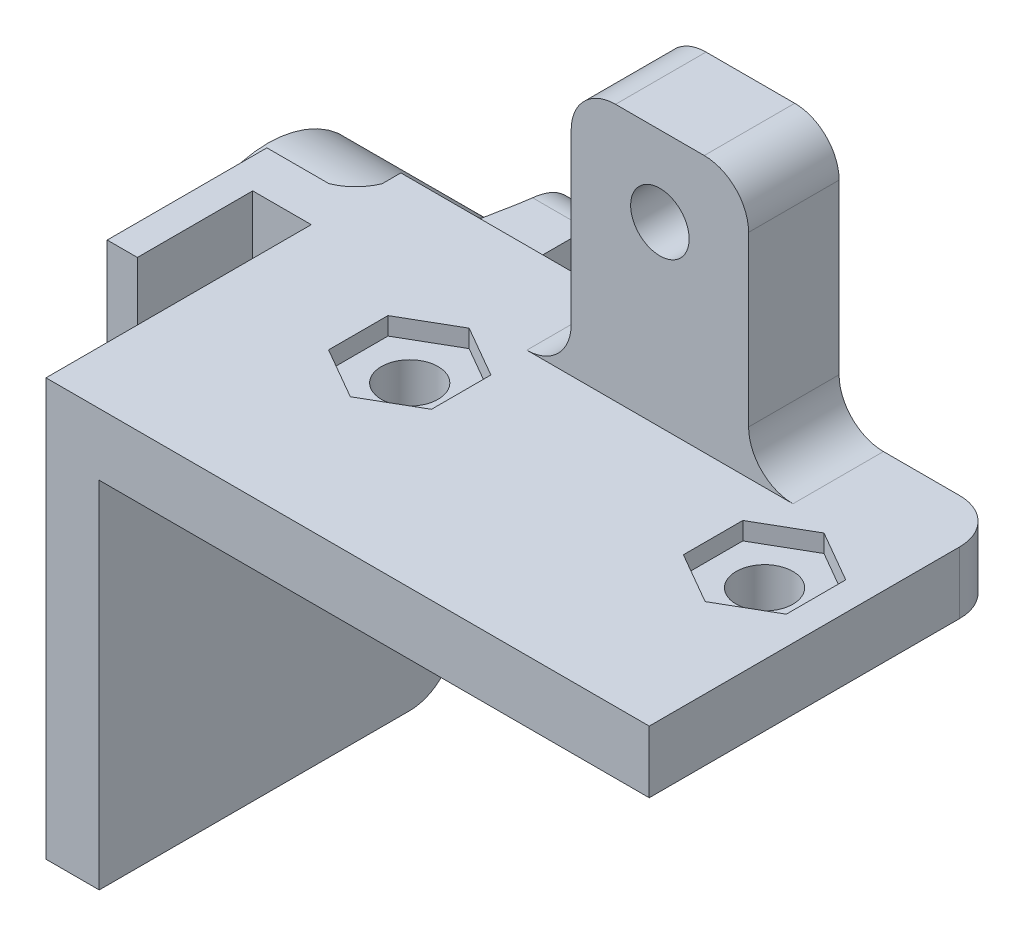
SolidWorks part; units mm, degrees
ref_plane "Alzado" through (0, 0, 0) normal (0, 0, 1) x (1, 0, 0)
ref_plane "Planta" through (0, 0, 0) normal (0, 1, 0) x (1, 0, 0)
ref_plane "Vista lateral" through (0, 0, 0) normal (1, 0, 0) x (0, 0, -1)
sketch "Croquis1" plane through (0, 0, 0) normal (0, 1, 0) x (1, 0, 0)
  line L1 (0, 0) -> (34, 0)
  line L2 (0, 0) -> (0, -20)
  line L3 (0, -20) -> (34, -20)
  line L4 (34, 0) -> (34, -20)
  dimension "D1" = 34
  dimension "D2" = 20
extrude "Saliente-Extruir1" add sketch "Croquis1" along normal blind 3.5
sketch "Croquis2" plane through (0, 3.5, 0) normal (0, 1, 0) x (1, 0, 0)
  line L0 (0, 0) -> (0, -20) construction
  line L1 (0, -20) -> (34, -20) construction
  circle A0 centre (9.5, -9) radius 1.6
  circle A1 centre (29.5, -9) radius 1.6
  dimension "D1" = 3.2
  dimension "D2" = 3.2
  dimension "D3" = 20
  dimension "D4" = 9.5
  dimension "D5" = 11
extrude "Cortar-Extruir1" cut sketch "Croquis2" against normal up to surface (3.5 mm away) up to face at (17, 0, 10)
sketch "Croquis3" plane through (0, 0, 0) normal (0, -1, 0) x (1, 0, 0)
  line L0 (0, 20) -> (34, 20) construction
  line L1 (0, 0) -> (3, 0)
  line L2 (0, 0) -> (0, 20)
  line L3 (0, 20) -> (3, 20)
  line L4 (3, 0) -> (3, 20)
  dimension "D1" = 3
extrude "Saliente-Extruir2" add sketch "Croquis3" along normal blind 20
sketch "Croquis4" plane through (0, 0, 0) normal (0, 0, -1) x (-1, 0, 0)
  line L0 (-3, -20) -> (-3, 0) construction
  line L1 (-3, -1.5) -> (0, -1.5)
  line L2 (-3, -1.5) -> (-3, -15.5)
  line L3 (-3, -15.5) -> (0, -15.5)
  line L4 (0, -1.5) -> (0, -15.5)
  line L5 (0, 3.5) -> (0, -20) construction
  line L6 (-34, 3.5) -> (0, 3.5) construction
  dimension "D1" = 14
  dimension "D2" = 5
extrude "Saliente-Extruir3" add sketch "Croquis4" along normal blind 10
sketch "Croquis5" plane through (0, 0, 0) normal (-1, 0, 0) x (0, 0, 1)
  line L0 (-10, -15.5) -> (0, -15.5) construction
  line L1 (0, 3.5) -> (0, -1.5) construction
  circle A0 centre (-3.5, -8.3) radius 6
  dimension "D1" = 12
  dimension "D2" = 7.2
  dimension "D3" = 3.5
extrude "Saliente-Extruir4" add sketch "Croquis5" along normal blind 11
sketch "Croquis6" plane through (-11, 0, 0) normal (-1, 0, 0) x (0, 0, 1)
  circle A0 centre (-3.5, -8.3) radius 1
  dimension "D1" = 2
extrude "Cortar-Extruir2" cut sketch "Croquis6" against normal up to surface (14 mm away) up to face at (3, -9.25, 2.5)
sketch "Croquis7" plane through (3, 0, 0) normal (1, 0, 0) x (0, 0, -1)
  line L0 (10, -1.5) -> (10, -15.5) construction
  line L1 (7.1, -12.9) -> (0.8, -12.9)
  line L2 (7.1, -12.9) -> (7.1, -4.6)
  line L3 (7.1, -4.6) -> (0.8, -4.6)
  line L4 (0.8, -12.9) -> (0.8, -4.6)
  line L5 (10, -15.5) -> (0, -15.5) construction
  dimension "D1" = 8.3
  dimension "D2" = 6.3
  dimension "D3" = 2.9
  dimension "D4" = 2.6
extrude "Cortar-Extruir3" cut sketch "Croquis7" against normal blind 6.4
sketch "Croquis8" plane through (-11, 0, 0) normal (-1, 0, 0) x (0, 0, 1)
  circle A0 centre (-3.5, -8.3) radius 4.2
  dimension "D1" = 8.4
extrude "Cortar-Extruir4" cut sketch "Croquis8" against normal blind 6.3
fillet "Redondeo1" radius 1 1 edges at (-3.4, -8.3, -4.5)
sketch "Croquis9" plane through (0, 0, 0) normal (-1, 0, 0) x (0, 0, 1)
  line L0 (20, -20) -> (0, -20) construction
  line L1 (2.55, -20) -> (11.55, -20)
  line L2 (2.55, -20) -> (2.55, 3.5)
  line L3 (2.55, 3.5) -> (11.55, 3.5)
  line L4 (11.55, -20) -> (11.55, 3.5)
  line L5 (0, 3.5) -> (20, 3.5) construction
  line L6 (0, 3.5) -> (0, -1.5) construction
  dimension "D1" = 9
  dimension "D2" = 2.55
extrude "Saliente-Extruir7" add sketch "Croquis9" along normal blind 5
sketch "Croquis10" plane through (0, 0, 11.55) normal (0, 0, 1) x (1, 0, 0)
  line L5 (-5, -20) -> (0, -20) construction
  line L6 (0, 3.5) -> (-3.3, 3.5)
  line L7 (0, 3.5) -> (0, -20)
  line L8 (0, -20) -> (-3.3, -20)
  line L9 (-3.3, 3.5) -> (-3.3, -20)
  dimension "D1" = 3.3
extrude "Cortar-Extruir5" cut sketch "Croquis10" against normal blind 6.5
sketch "Croquis11" plane through (0, 3.5, 0) normal (0, 1, 0) x (1, 0, 0)
  line L0 (34, 0) -> (0, 0) construction
  line L1 (24.7, 0) -> (14.7, 0)
  line L2 (24.7, 0) -> (24.7, -5.1)
  line L3 (24.7, -5.1) -> (14.7, -5.1)
  line L4 (14.7, 0) -> (14.7, -5.1)
  line L5 (34, -20) -> (34, 0) construction
  dimension "D1" = 10
  dimension "D2" = 5.1
  dimension "D3" = 9.3
extrude "Saliente-Extruir8" add sketch "Croquis11" along normal blind 14.5
sketch "Croquis12" plane through (0, 0, 0) normal (0, 0, -1) x (-1, 0, 0)
  line L0 (-24.7, 18) -> (-24.7, 3.5) construction
  line L1 (-34, 3.5) -> (-24.7, 3.5) construction
  circle A0 centre (-19.7, 13.5) radius 1.65
  dimension "D2" = 3.3
  dimension "D1" = 5
  dimension "D3" = 10
extrude "Cortar-Extruir6" cut sketch "Croquis12" against normal up to surface (5.1 mm away) up to face at (19.7, 10.75, 5.1)
sketch "Croquis13" plane through (0, 0, 0) normal (0, 0, -1) x (-1, 0, 0)
  circle A0 centre (-19.7, 13.5) radius 3
  dimension "D1" = 6
extrude "Cortar-Extruir7" cut sketch "Croquis13" against normal blind 2.6
sketch "Croquis15" plane through (0, 3.5, 0) normal (0, 1, 0) x (1, 0, 0)
  line L1 (9.5, -5.6514) -> (6.6, -7.3257)
  line L2 (6.6, -7.3257) -> (6.6, -10.6743)
  line L3 (6.6, -10.6743) -> (9.5, -12.3486)
  line L4 (9.5, -12.3486) -> (12.4, -10.6743)
  line L5 (12.4, -10.6743) -> (12.4, -7.3257)
  line L6 (12.4, -7.3257) -> (9.5, -5.6514)
  line L7 (29.5, -5.6514) -> (26.6, -7.3257)
  line L8 (26.6, -7.3257) -> (26.6, -10.6743)
  line L9 (26.6, -10.6743) -> (29.5, -12.3486)
  line L10 (29.5, -12.3486) -> (32.4, -10.6743)
  line L11 (32.4, -10.6743) -> (32.4, -7.3257)
  line L12 (32.4, -7.3257) -> (29.5, -5.6514)
  circle A0 centre (9.5, -9) radius 2.9 construction
  circle A1 centre (29.5, -9) radius 2.9 construction
  dimension "D1" = 5.8
  dimension "D2" = 5.8
extrude "Cortar-Extruir9" cut sketch "Croquis15" against normal blind 1
fillet "Redondeo3" radius 2.5 2 edges at (1.5, -15.5, -10) (1.5, -1.5, -10)
fillet "Redondeo5" radius 2.5 1 edges at (0, -8.3, -9.5)
sketch "Croquis16" plane through (0, -20, 0) normal (0, -1, 0) x (1, 0, 0)
  line L0 (-5, 2.55) -> (0, 2.55) construction
  line L2 (0, 2.55) -> (0, 0) construction
  line L3 (0, 1.05) -> (0, 2.55)
  line L4 (0, 2.55) -> (-1.5, 2.55)
  arc A0 (-1.5, 2.55) -> (0, 1.05) centre (-2.5583, -0.0083) cw
  dimension "D1" = 1.5
  dimension "D2" = 1.5
extrude "Saliente-Extruir9" add sketch "Croquis16" against normal up to surface (23.5 mm away) up to face at (9.5, 3.5, 9)
fillet "Redondeo6" radius 2.5 6 edges at (14.7, 3.5, 2.55) (24.7, 3.5, 2.55) (24.7, 18, 2.55) (14.7, 18, 2.55) (1.5, -20, 0) (34, 1.75, 0)
